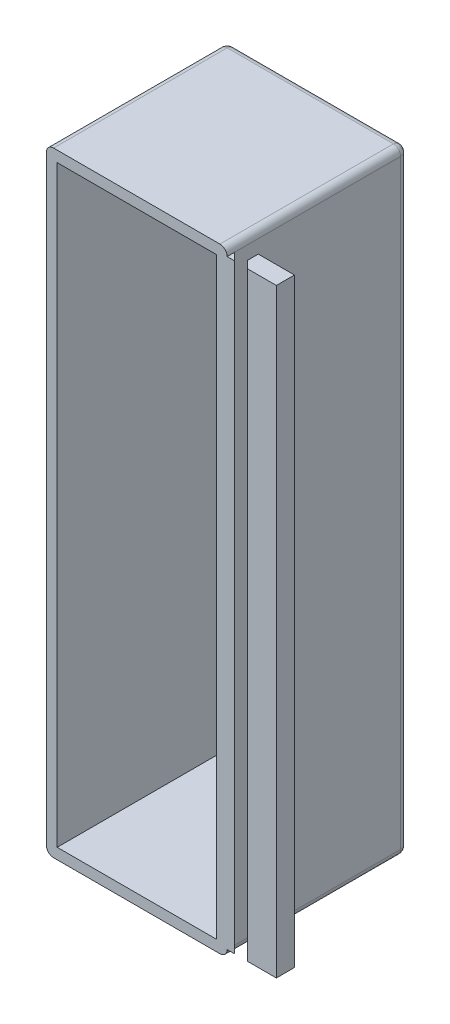
SolidWorks part; units mm, degrees
ref_plane "Front Plane" through (0, 0, 0) normal (0, 0, 1) x (1, 0, 0)
ref_plane "Top Plane" through (0, 0, 0) normal (0, 1, 0) x (1, 0, 0)
ref_plane "Right Plane" through (0, 0, 0) normal (1, 0, 0) x (0, 0, -1)
sketch "Sketch2" plane through (0, 0, 0) normal (0, 0, 1) x (1, 0, 0)
  line L1 (25, 85) -> (-25, 85)
  line L2 (25, 85) -> (25, -85)
  line L3 (25, -85) -> (-25, -85)
  line L4 (-25, 85) -> (-25, -85)
  line L5 (25, 85) -> (-25, -85) construction
  line L6 (25, -85) -> (-25, 85) construction
  point P0 (0, 0)
  dimension "D1" = 50
  dimension "D2" = 170
extrude "Boss-Extrude1" add sketch "Sketch2" along normal blind 50
sketch "Sketch3" plane through (0, 0, 50) normal (0, 0, 1) x (1, 0, 0)
  line L0 (25, 85) -> (-25, 85) construction
  line L1 (-22, 82) -> (22, 82)
  line L2 (-22, 82) -> (-22, -82)
  line L3 (-22, -82) -> (22, -82)
  line L4 (22, 82) -> (22, -82)
  line L5 (-25, -85) -> (25, -85) construction
  line L6 (25, -85) -> (25, 85) construction
  line L7 (-25, 85) -> (-25, -85) construction
  dimension "D1" = 3
  dimension "D2" = 3
  dimension "D3" = 3
  dimension "D4" = 3
extrude "Cut-Extrude1" cut sketch "Sketch3" against normal blind 47
fillet "Fillet2" radius 2 8 edges at (25, -85, 25) (25, 0, 0) (0, -85, 0) (-25, -85, 25) (-25, 0, 0) (25, 85, 25) (0, 85, 0) (-25, 85, 25)
sketch "Sketch4" plane through (25, 0, 0) normal (1, 0, 0) x (0, 0, -1)
  line L0 (-50, -83) -> (-2, -83) construction
  line L1 (-50, 83) -> (-48, 83)
  line L2 (-50, 83) -> (-50, -83)
  line L3 (-50, -83) -> (-48, -83)
  line L4 (-48, 83) -> (-48, -83)
  dimension "D1" = 2
extrude "Boss-Extrude2" add sketch "Sketch4" along normal blind 2
sketch "Sketch5" plane through (0, -83, 0) normal (0, -1, 0) x (1, 0, 0)
  line L0 (25, 48) -> (27, 50)
  line L1 (27, 50) -> (27, 48) construction
  line L2 (27, 50) -> (27, 48)
  line L3 (27, 48) -> (25, 48) construction
  line L4 (27, 48) -> (25, 48)
extrude "Cut-Extrude2" cut sketch "Sketch5" against normal blind 170
sketch "Sketch6" plane through (0, 0, 50) normal (0, 0, 1) x (1, 0, 0)
  line L0 (27, -83) -> (25, -83) construction
  line L1 (28.617, 82.8957) -> (38.617, 82.8957)
  line L2 (28.617, 82.8957) -> (28.617, -83)
  line L3 (28.617, -83) -> (38.617, -83)
  line L4 (38.617, 82.8957) -> (38.617, -83)
  dimension "D1" = 0
  dimension "D2" = 10
extrude "Boss-Extrude3" add sketch "Sketch6" against normal blind 5 separate body
sketch "Sketch8" plane through (0, -83, 0) normal (0, -1, 0) x (-1, 0, 0)
  line L0 (-25, -48) -> (-28.617, -48) construction
  line L1 (-28.617, -45) -> (-28.617, -50) construction
  line L2 (-28.617, -48) -> (-30.617, -50)
  line L3 (-30.617, -50) -> (-28.617, -50)
  line L4 (-28.617, -50) -> (-28.617, -48)
extrude "Cut-Extrude4" cut sketch "Sketch8" against normal blind 180
